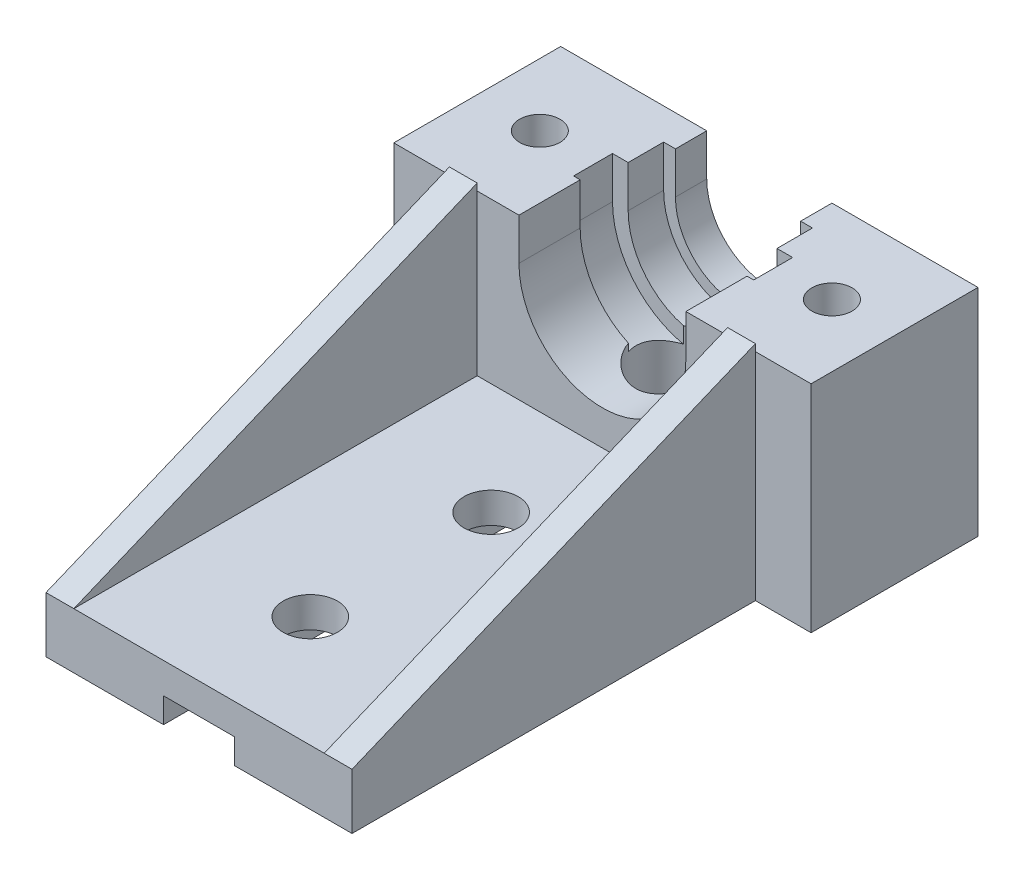
SolidWorks part; units mm, degrees
ref_plane "Front Plane" through (0, 0, 0) normal (0, 0, 1) x (1, 0, 0)
ref_plane "Top Plane" through (0, 0, 0) normal (0, 1, 0) x (1, 0, 0)
ref_plane "Right Plane" through (0, 0, 0) normal (1, 0, 0) x (0, 0, -1)
sketch "Sketch1" plane through (0, 0, 0) normal (0, 0, 1) x (1, 0, 0)
  line L0 (-5.2806, 25) -> (-5.2806, 41)
  line L2 (-5.2806, 41) -> (5.2194, 41)
  line L3 (24.7194, 41) -> (24.7194, 25)
  line L5 (24.7194, 25) -> (12.2694, 25)
  line L6 (12.2694, 25) -> (12.2694, 26.8)
  line L7 (12.2694, 26.8) -> (7.1694, 26.8)
  line L8 (7.1694, 26.8) -> (7.1694, 25)
  line L9 (7.1694, 25) -> (-5.2806, 25)
  line L10 (9.7194, 26.8) -> (9.7194, 48.2) construction
  line L11 (14.2194, 41) -> (24.7194, 41)
  line L13 (5.2194, 37.5) -> (5.2194, 41)
  line L15 (14.2194, 37.5) -> (14.2194, 41)
  arc A0 (5.2194, 37.5) -> (14.2194, 37.5) centre (9.7194, 37.5) ccw
  dimension "D3" = 4.5
  dimension "D1" = 5.1
  dimension "D2" = 1.8
  dimension "D4" = 16
  dimension "D5" = 30
  dimension "D6" = 3.5
extrude "Boss-Extrude1" add sketch "Sketch1" against normal blind 12 contours L13 L2 L0 L9 L8 L7 L6 L5 L3 L11 L15 A0
sketch "Sketch2" plane through (0, 0, 0) normal (0, 0, 1) x (1, 0, 0)
  line L0 (14.2194, 41) -> (24.7194, 41) construction
  line L2 (4.3694, 37.5) -> (4.3694, 41)
  line L3 (4.3694, 41) -> (15.0694, 41)
  line L4 (15.0694, 37.5) -> (15.0694, 41)
  arc A0 (4.3694, 37.5) -> (15.0694, 37.5) centre (9.7194, 37.5) ccw
  dimension "D1" = 10.7
extrude "Cut-Extrude1" cut sketch "Sketch2" against normal blind 9.75
sketch "Sketch7" plane through (0, 0, 0) normal (0, 0, 1) x (1, 0, 0)
  line L1 (15.0694, 41) -> (24.7194, 41) construction
  line L2 (3.2444, 37.5) -> (3.2444, 41)
  line L3 (3.2444, 41) -> (16.1944, 41)
  line L4 (16.1944, 37.5) -> (16.1944, 41)
  arc A0 (3.2444, 37.5) -> (16.1944, 37.5) centre (9.7194, 37.5) ccw
  arc A1 (14.2194, 37.5) -> (5.2194, 37.5) centre (9.7194, 37.5) ccw construction
  dimension "D1" = 12.95
extrude "Cut-Extrude4" cut sketch "Sketch7" against normal blind 2.8 from offset 4.4 offset against normal yes
sketch "Sketch8" plane through (0, 0, 0) normal (0, 0, 1) x (1, 0, 0)
  line L0 (15.0694, 41) -> (24.7194, 41) construction
  line L2 (3.7194, 37.5) -> (3.7194, 41)
  line L3 (3.7194, 41) -> (15.7194, 41)
  line L4 (15.7194, 37.5) -> (15.7194, 41)
  arc A0 (3.7194, 37.5) -> (15.7194, 37.5) centre (9.7194, 37.5) ccw
  arc A2 (14.2194, 37.5) -> (5.2194, 37.5) centre (9.7194, 37.5) ccw construction
  dimension "D1" = 12
sketch "Sketch3" plane through (0, 41, 0) normal (0, 1, 0) x (1, 0, 0)
  line L0 (24.7194, 6) -> (-5.2806, 6) construction
  line L1 (24.7194, 12) -> (24.7194, 0) construction
  line L2 (-5.2806, 12) -> (-5.2806, 0) construction
  line L3 (5.2194, 12) -> (14.2194, 12) construction
  line L4 (9.7194, 12) -> (9.7194, 0) construction
  circle A0 centre (20.2194, 6) radius 1.45
  circle A1 centre (-0.7806, 6) radius 1.45
  dimension "D2" = 2.9
  dimension "D1" = 4.5
extrude "Cut-Extrude2" cut sketch "Sketch3" against normal blind 18
sketch "Sketch4" plane through (0, 0, 0) normal (0, 0, 1) x (1, 0, 0)
  line L0 (-1.2806, 25) -> (-1.2806, 29)
  line L1 (7.1694, 25) -> (-5.2806, 25) construction
  line L2 (-1.2806, 29) -> (20.7194, 29)
  line L5 (12.2694, 26.8) -> (7.1694, 26.8)
  line L6 (7.1694, 26.8) -> (7.1694, 25)
  line L7 (7.1694, 25) -> (-1.2806, 25)
  line L8 (12.2694, 25) -> (20.7194, 25)
  line L9 (12.2694, 26.8) -> (12.2694, 25)
  line L10 (20.7194, 25) -> (20.7194, 29)
  dimension "D2" = 4
extrude "Boss-Extrude2" add sketch "Sketch4" along normal blind 29
sketch "Sketch5" plane through (0, 29, 0) normal (0, 1, 0) x (1, 0, 0)
  line L0 (9.7194, -29) -> (9.7194, 0) construction
  line L1 (20.7194, -29) -> (-1.2806, -29) construction
  line L2 (20.7194, 0) -> (-1.2806, 0) construction
  circle A0 centre (9.7194, -21) radius 1.95
  circle A1 centre (9.7194, -8) radius 1.95
  circle A3 centre (9.7194, 5) radius 2.6
  dimension "D1" = 3.9
  dimension "D5" = 5.2
  dimension "D2" = 13
  dimension "D3" = 8
  dimension "D4" = 13
extrude "Cut-Extrude3" cut sketch "Sketch5" against normal mid plane 29
sketch "Sketch6" plane through (-1.2806, 0, 0) normal (-1, 0, 0) x (0, 0, 1)
  line L0 (29, 29) -> (0, 41)
  line L1 (0, 41) -> (0, 29)
  line L2 (0, 29) -> (29, 29)
extrude "Boss-Extrude3" add sketch "Sketch6" against normal blind 2
extrude "Boss-Extrude4" add sketch "Sketch6<2>" along normal blind 2 from offset 22 offset against normal yes
sketch "Sketch6<2>" plane through (-1.2806, 0, 0) normal (-1, 0, 0) x (0, 0, 1) same geometry as "Sketch6"
extrude "Cut-Extrude5" cut sketch "Sketch8" against normal blind 5.2
sketch "Sketch9" plane through (0, 41, 0) normal (0, 1, 0) x (1, 0, 0)
  line L0 (14.2194, 12) -> (24.7194, 12) construction
  line L1 (24.7194, 12) -> (-5.2806, 12)
  line L2 (24.7194, 12) -> (24.7194, 0)
  line L3 (24.7194, 0) -> (-5.2806, 0)
  line L4 (-5.2806, 12) -> (-5.2806, 0)
  line L5 (-5.2806, 0) -> (-1.2806, 0) construction
extrude "Cut-Extrude6" cut sketch "Sketch9" against normal blind 0.5
